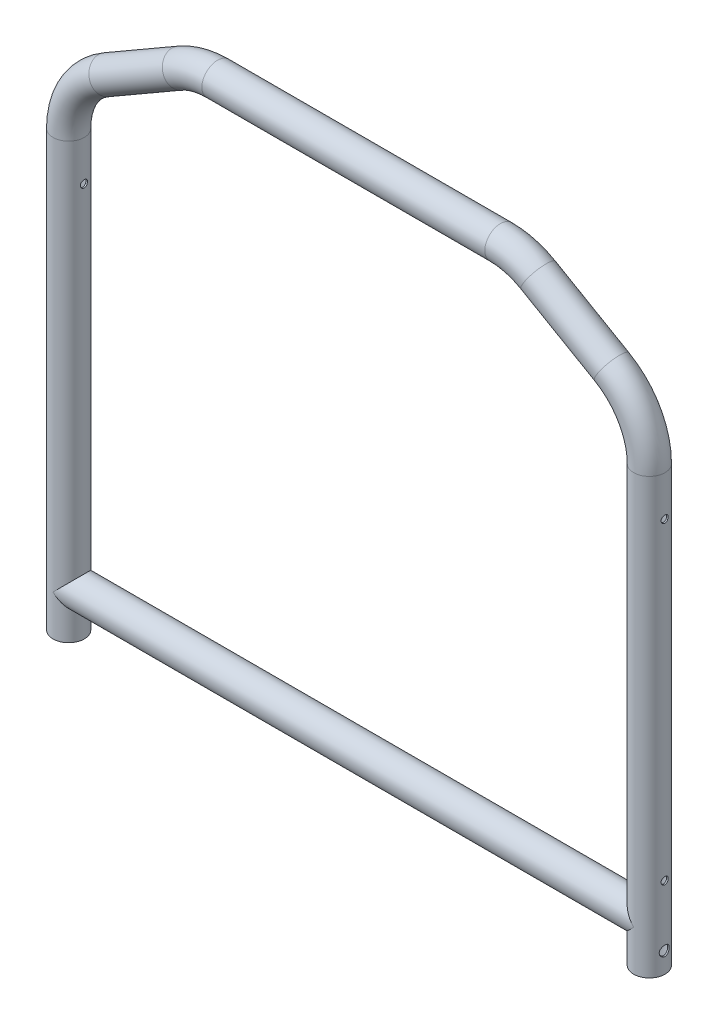
SolidWorks part; units mm, degrees
ref_plane "Front Plane" through (0, 0, 0) normal (0, 0, 1) x (1, 0, 0)
ref_plane "Top Plane" through (0, 0, 0) normal (0, 1, 0) x (1, 0, 0)
ref_plane "Right Plane" through (0, 0, 0) normal (1, 0, 0) x (0, 0, -1)
sketch "Sketch1" plane through (0, 0, 0) normal (0, 0, 1) x (1, 0, 0)
  line L0 (-99.3894, 0) -> (99.3894, 0)
  line L1 (125.8894, -7.1007) -> (177.5, -36.898)
  line L2 (204, -82.7974) -> (204, -388)
  line L3 (0, 0) -> (0, -391.4251) construction
  line L4 (-204, -82.7974) -> (-204, -388)
  line L5 (-125.8894, -7.1007) -> (-177.5, -36.898)
  arc A0 (204, -82.7974) -> (177.5, -36.898) centre (151, -82.7974) ccw
  arc A1 (125.8894, -7.1007) -> (99.3894, 0) centre (99.3894, -53) ccw
  arc A2 (-125.8894, -7.1007) -> (-99.3894, 0) centre (-99.3894, -53) cw
  arc A3 (-204, -82.7974) -> (-177.5, -36.898) centre (-151, -82.7974) cw
  dimension "D2" = 53
  dimension "D1" = 388
  dimension "D3" = 150
  dimension "D4" = 204
ref_plane "Plane1" through (204, -388, 0) normal (0, -1, 0) x (-1, 0, 0)
sketch "Sketch2" plane through (204, -388, 0) normal (0, -1, 0) x (-1, 0, 0)
  line L0 (0, 0) -> (26.5, 0) construction
  circle A0 centre (0, 0) radius 11
  circle A1 centre (0, 0) radius 10
  dimension "D1" = 1
sweep "Sweep1" add profiles "Sketch2" path "Sketch1"
sketch "Sketch3" plane through (0, 0, 0) normal (1, 0, 0) x (0, 0, -1)
  circle A0 centre (0, -359.3992) radius 11
  circle A1 centre (0, -359.3992) radius 10
  dimension "D1" = 1
extrude "Boss-Extrude1" add sketch "Sketch3" along normal up to surface and the other way up to surface up to face at (215, -388, 0) other way up to face at (-215, -82.7974, 0)
sketch "Sketch4" plane through (0, -388, 0) normal (0, -1, 0) x (1, 0, 0)
  line L0 (-204, 0) -> (-214, 0) construction
  circle A0 centre (-204, 0) radius 10 construction
ref_plane "Plane2" through (-204, -388, 0) normal (-1, 0, 0) x (0, 0, 1)
sketch "Sketch5" plane through (-204, -388, 0) normal (-1, 0, 0) x (0, 0, 1)
  circle A0 centre (0, 57) radius 2.5
  circle A1 centre (0, 388) radius 11 construction
  circle A2 centre (0, 14.3032) radius 3.5
  dimension "D1" = 331
extrude "Cut-Extrude1" cut sketch "Sketch5" along normal blind 200
sketch "Sketch6" plane through (-204, -388, 0) normal (-1, 0, 0) x (0, 0, 1)
  circle A0 centre (0, 277) radius 2.5
  circle A1 centre (0, 388) radius 11 construction
  dimension "D1" = 111
extrude "Cut-Extrude2" cut sketch "Sketch6" against normal blind 200 and the other way blind 200
mirror "Mirror1" about plane through (0, 0, 0) normal (1, 0, 0) of "Cut-Extrude2", "Cut-Extrude1"
